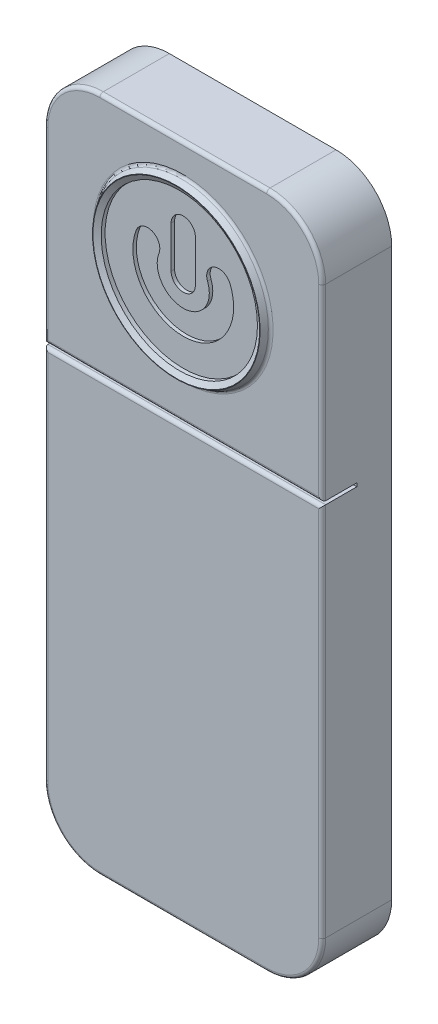
SolidWorks part; units mm, degrees
ref_plane "Front Plane" through (0, 0, 0) normal (0, 0, 1) x (1, 0, 0)
ref_plane "Top Plane" through (0, 0, 0) normal (0, 1, 0) x (1, 0, 0)
ref_plane "Right Plane" through (0, 0, 0) normal (1, 0, 0) x (0, 0, -1)
sketch "Sketch1" plane through (0, 0, 0) normal (0, 0, 1) x (1, 0, 0)
  line L1 (0, 0) -> (8, 0)
  line L2 (0, 0) -> (0, 19.5)
  line L3 (0, 19.5) -> (8, 19.5)
  line L4 (8, 0) -> (8, 19.5)
  dimension "D1" = 19.5
  dimension "D2" = 8
extrude "Boss-Extrude1" add sketch "Sketch1" along normal blind 2
fillet "Fillet1" radius 1.6 4 edges at (8, 0, 1) (0, 0, 1) (8, 19.5, 1) (0, 19.5, 1)
sketch "Sketch3" plane through (0, 0, 2) normal (0, 0, 1) x (1, 0, 0)
  line L0 (4, 17.3) -> (4, 16.1) construction
  line L1 (4.35, 17.3) -> (4.35, 16.1)
  line L2 (3.65, 17.3) -> (3.65, 16.1)
  line L3 (0, 17.9) -> (0, 1.6) construction
  line L4 (2.9753, 16.5) -> (5.0247, 16.5) construction
  line L5 (6.4, 19.5) -> (1.6, 19.5) construction
  arc A0 (4.35, 17.3) -> (3.65, 17.3) centre (4, 17.3) ccw
  arc A1 (3.65, 16.1) -> (4.35, 16.1) centre (4, 16.1) ccw
  arc A2 (2.9753, 16.5) -> (5.0247, 16.5) centre (4, 16.1) ccw construction
  arc A3 (2.6493, 16.6273) -> (5.3507, 16.6273) centre (4, 16.1) ccw
  arc A4 (3.3013, 16.3727) -> (4.6987, 16.3727) centre (4, 16.1) ccw
  arc A5 (3.3013, 16.3727) -> (2.6493, 16.6273) centre (2.9753, 16.5) ccw
  arc A6 (5.3507, 16.6273) -> (4.6987, 16.3727) centre (5.0247, 16.5) ccw
  point P2 (4, 16.7)
  point P10 (4, 15)
  dimension "D2" = 0.35
  dimension "D3" = 1.1
  dimension "D6" = 3
  dimension "D1" = 4
  dimension "D4" = 2.2
  dimension "D5" = 3.4
extrude "Cut-Extrude1" cut sketch "Sketch3" against normal blind 0.1
sketch "Sketch4" plane through (0, 0, 2) normal (0, 0, 1) x (1, 0, 0)
  circle A0 centre (4, 16.1) radius 2.25
  circle A1 centre (4, 16.1) radius 2.5
  dimension "D1" = 5
  dimension "D2" = 4.5
extrude "Boss-Extrude2" add sketch "Sketch4" along normal blind 0.2
chamfer "Chamfer1" distance 0.15 angle 30 2 edges at (6.25, 16.1, 2.2) (6.5, 16.1, 2.2)
sketch "Sketch5" plane through (0, 0, 2) normal (0, 0, 1) x (1, 0, 0)
  line L0 (0, 17.9) -> (0, 1.6) construction
  line L1 (0, 12.5) -> (8, 12.5)
  line L2 (0, 12.5) -> (0, 12.4)
  line L3 (0, 12.4) -> (8, 12.4)
  line L4 (8, 12.5) -> (8, 12.4)
  line L5 (8, 1.6) -> (8, 17.9) construction
  line L6 (6.4, 19.5) -> (1.6, 19.5) construction
  dimension "D1" = 0.1
  dimension "D2" = 7
extrude "Cut-Extrude2" cut sketch "Sketch5" against normal blind 1
fillet "Fillet2" radius 0.1 13 edges at (0.4686, 19.0314, 2) (4, 19.5, 2) (7.5314, 19.0314, 2) (8, 15.2, 2) (4, 12.5, 2) (0, 15.2, 2) (1.5, 16.1, 2) (7.5314, 0.4686, 2) (4, 0, 2) (0.4686, 0.4686, 2) (0, 7, 2) (4, 12.4, 2) (8, 7, 2)
